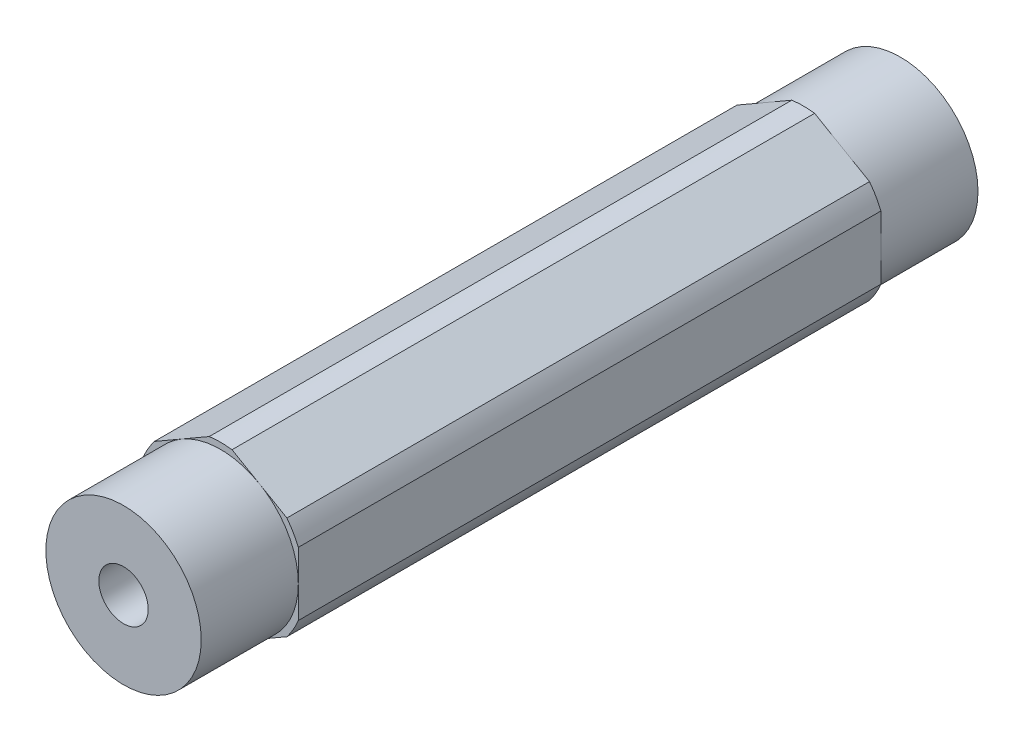
SolidWorks part; units mm, degrees
ref_plane "Front Plane" through (0, 0, 0) normal (0, 0, 1) x (1, 0, 0)
ref_plane "Top Plane" through (0, 0, 0) normal (0, 1, 0) x (1, 0, 0)
ref_plane "Right Plane" through (0, 0, 0) normal (1, 0, 0) x (0, 0, -1)
sketch "Sketch1" plane through (0, 0, 0) normal (0, 0, 1) x (1, 0, 0)
  line L1 (0, 7.3323) -> (-6.35, 3.6662)
  line L2 (-6.35, 3.6662) -> (-6.35, -3.6662)
  line L3 (-6.35, -3.6662) -> (0, -7.3323)
  line L4 (0, -7.3323) -> (6.35, -3.6662)
  line L5 (6.35, -3.6662) -> (6.35, 3.6662)
  line L6 (6.35, 3.6662) -> (0, 7.3323)
  circle A0 centre (0, 0) radius 6.35 construction
  circle A1 centre (0, 0) radius 6.858
  circle A2 centre (0, 0) radius 2.0193
  dimension "D1" = 12.7
  dimension "D2" = 13.716
  dimension "D3" = 4.0386
extrude "Boss-Extrude1" add sketch "Sketch1" along normal mid plane 47.625 contours L5 A1 L6 L1 L2 L3 L4 region at (0, 6.6711, 0)
sketch "Sketch2" plane through (0, 0, 23.8125) normal (0, 0, 1) x (1, 0, 0)
  circle A0 centre (0, 0) radius 6.35
  circle A1 centre (0, 0) radius 2.0193
  dimension "D1" = 12.7
  dimension "D2" = 4.0386
extrude "Boss-Extrude2" add sketch "Sketch2" along normal blind 7.9375
mirror "Mirror1" about plane through (0, 0, 0) normal (0, 0, 1) of "Boss-Extrude2"
